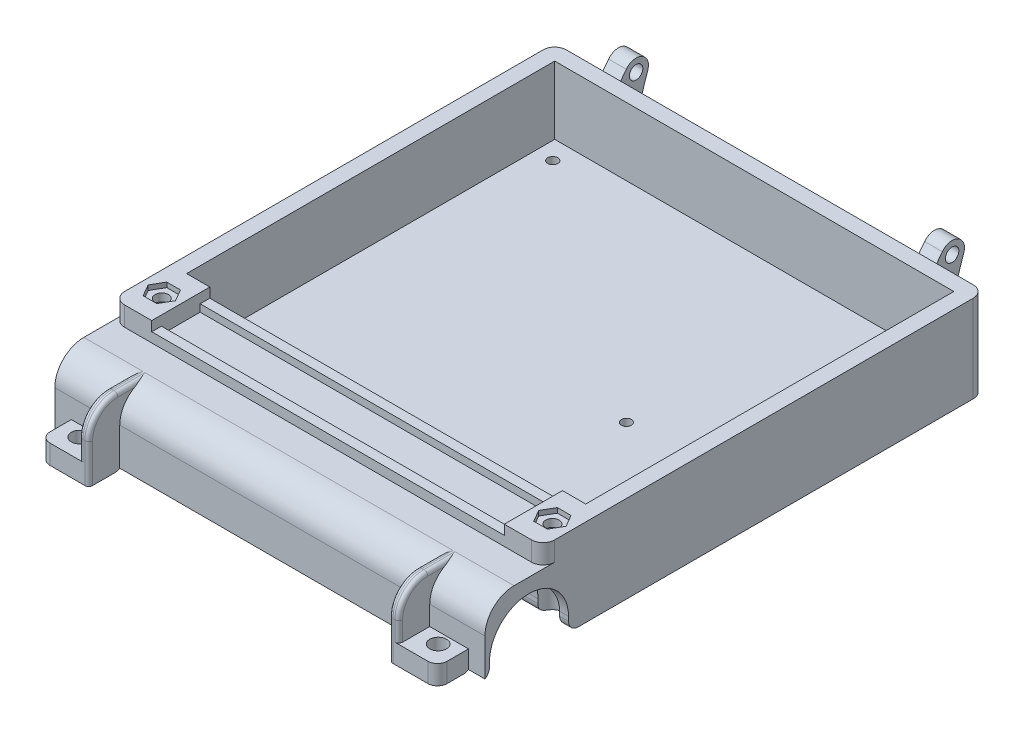
SolidWorks part; units mm, degrees
ref_plane "Front Plane" through (0, 0, 0) normal (0, 0, 1) x (1, 0, 0)
ref_plane "Top Plane" through (0, 0, 0) normal (0, 1, 0) x (1, 0, 0)
ref_plane "Right Plane" through (0, 0, 0) normal (1, 0, 0) x (0, 0, -1)
sketch "Sketch1" plane through (0, 0, 0) normal (0, 1, 0) x (1, 0, 0)
  line L1 (-65.405, -57.15) -> (65.405, -57.15) construction
  line L2 (-65.405, -57.15) -> (-65.405, 57.15) construction
  line L3 (-65.405, 57.15) -> (65.405, 57.15) construction
  line L4 (65.405, -57.15) -> (65.405, 57.15) construction
  line L5 (-65.405, -57.15) -> (65.405, 57.15) construction
  line L6 (-65.405, 57.15) -> (65.405, -57.15) construction
  line L7 (-70.485, 62.23) -> (70.485, 62.23)
  line L8 (-70.485, 62.23) -> (-70.485, -82.55)
  line L9 (-70.485, -82.55) -> (70.485, -82.55)
  line L10 (70.485, 62.23) -> (70.485, -82.55)
  circle A0 centre (61.595, 50.8) radius 1.65
  circle A1 centre (-59.69, 50.8) radius 1.65
  circle A2 centre (26.67, -11.43) radius 1.65
  point P0 (0, 0)
  dimension "D5" = 3.3
  dimension "D1" = 114.3
  dimension "D2" = 130.81
  dimension "D3" = 92.075
  dimension "D4" = 127
  dimension "D6" = 5.08
  dimension "D7" = 5.08
  dimension "D8" = 5.08
  dimension "D9" = 107.95
  dimension "D10" = 5.715
  dimension "D11" = 45.72
  dimension "D12" = 25.4
extrude "Boss-Extrude1" add sketch "Sketch1" along normal blind 6.35
sketch "Sketch2" plane through (0, 6.35, 0) normal (0, 1, 0) x (1, 0, 0)
  line L0 (70.485, -82.55) -> (70.485, 62.23) construction
  line L2 (-70.485, 62.23) -> (-70.485, -82.55) construction
  line L3 (70.485, 62.23) -> (-70.485, 62.23) construction
  line L4 (70.485, -82.55) -> (70.485, 62.23)
  line L5 (-70.485, -82.55) -> (70.485, -82.55)
  line L6 (-70.485, 62.23) -> (-70.485, -82.55)
  line L7 (70.485, 62.23) -> (-70.485, 62.23)
  line L8 (57.785, -79.375) -> (57.785, -66.675)
  line L9 (65.405, 57.15) -> (-65.405, 57.15)
  line L10 (-65.405, 57.15) -> (-65.405, -63.5)
  line L12 (-65.405, -63.5) -> (65.405, -63.5)
  line L13 (-57.785, -79.375) -> (57.785, -79.375)
  line L14 (57.785, -66.675) -> (-57.785, -66.675)
  line L15 (-57.785, -66.675) -> (-57.785, -79.375)
  line L16 (65.405, -63.5) -> (65.405, 57.15)
  dimension "D2" = 3.175
  dimension "D1" = 5.08
  dimension "D3" = 5.08
  dimension "D4" = 5.08
  dimension "D5" = 12.7
  dimension "D6" = 3.175
  dimension "D7" = 12.7
  dimension "D8" = 12.7
extrude "Boss-Extrude2" add sketch "Sketch2" along normal blind 22.225
sketch "Sketch3" plane through (0, 28.575, 0) normal (0, 1, 0) x (1, 0, 0)
  line L0 (-65.405, -63.5) -> (65.405, -63.5) construction
  line L1 (-57.785, -63.5) -> (57.785, -63.5)
  line L2 (-57.785, -63.5) -> (-57.785, -82.55)
  line L3 (-57.785, -82.55) -> (57.785, -82.55)
  line L4 (57.785, -63.5) -> (57.785, -82.55)
  line L5 (-70.485, -82.55) -> (70.485, -82.55) construction
  line L7 (57.785, -79.375) -> (57.785, -66.675) construction
  line L8 (-57.785, -66.675) -> (-57.785, -79.375) construction
extrude "Cut-Extrude1" cut sketch "Sketch3" against normal blind 3.175
sketch "Sketch4" plane through (0, 6.35, 0) normal (0, 1, 0) x (1, 0, 0)
  line L4 (-57.785, -66.675) -> (-57.785, -79.375)
  line L5 (-57.785, -79.375) -> (57.785, -79.375)
  line L6 (57.785, -79.375) -> (57.785, -66.675)
  line L7 (57.785, -66.675) -> (-57.785, -66.675)
  line L8 (-57.785, -66.675) -> (-57.785, -79.375)
  line L9 (-57.785, -79.375) -> (57.785, -79.375)
  line L10 (57.785, -79.375) -> (57.785, -66.675)
  line L11 (57.785, -66.675) -> (-57.785, -66.675)
  dimension "D1" = 0
extrude "Boss-Extrude3" add sketch "Sketch4" along normal offset from surface (16.6687 mm away) 2.3813 up to face at (0, 25.4, 65.0875)
ref_plane "Plane1" through (51.7855, 0, 0) normal (1, 0, 0) x (0, 0, -1)
sketch "Sketch5" plane through (51.7855, 0, 0) normal (1, 0, 0) x (0, 0, -1)
  line L0 (-82.55, 28.575) -> (62.23, 28.575) construction
  line L1 (69.3307, 32.075) -> (65.2893, 32.075) construction
  line L2 (65.2893, 32.075) -> (63.2685, 28.575) construction
  line L3 (63.2685, 28.575) -> (65.2893, 25.075) construction
  line L4 (65.2893, 25.075) -> (69.3307, 25.075) construction
  line L5 (69.3307, 25.075) -> (71.3515, 28.575) construction
  line L6 (71.3515, 28.575) -> (69.3307, 32.075) construction
  line L7 (62.23, 28.575) -> (62.23, 0) construction
  line L8 (62.23, 28.575) -> (64.0948, 31.0236)
  line L9 (62.23, 0) -> (62.23, 28.575)
  line L10 (62.23, 0) -> (71.1518, 27.3204)
  circle A0 centre (67.31, 28.575) radius 3.5 construction
  arc A1 (64.0948, 31.0236) -> (71.1518, 27.3204) centre (67.31, 28.575) cw
  circle A2 centre (67.31, 28.575) radius 2.2
  dimension "D3" = 4.4
  dimension "D1" = 5.08
  dimension "D2" = 7
extrude "Boss-Extrude4" add sketch "Sketch5" along normal mid plane 5.8
mirror "Mirror1" about plane through (0, 0, 0) normal (1, 0, 0) of "Boss-Extrude4"
sketch "Sketch6" plane through (0, 0, 82.55) normal (0, 0, 1) x (1, 0, 0)
  line L0 (70.485, 28.575) -> (70.485, 0) construction
  line L1 (-70.485, 0) -> (70.485, 0)
  line L2 (-70.485, 0) -> (-70.485, 22.225)
  line L3 (-70.485, 22.225) -> (70.485, 22.225)
  line L4 (70.485, 0) -> (70.485, 22.225)
  dimension "D1" = 22.225
extrude "Boss-Extrude5" add sketch "Sketch6" along normal blind 19.05
sketch "Sketch7" plane through (0, 0, 0) normal (0, -1, 0) x (1, 0, 0)
  line L0 (0, 0) -> (0, 146.1519) construction
  line L1 (-70.485, 101.6) -> (70.485, 101.6) construction
  line L2 (52.3875, 101.6) -> (65.0875, 101.6)
  line L3 (52.3875, 101.6) -> (52.3875, 111.76)
  line L4 (52.3875, 111.76) -> (65.0875, 111.76)
  line L5 (65.0875, 101.6) -> (65.0875, 111.76)
  line L6 (52.3875, 105.2) -> (58.7375, 105.2) construction
  line L7 (58.7375, 105.2) -> (65.0875, 105.2) construction
  line L8 (-58.7375, 105.2) -> (-65.0875, 105.2) construction
  line L9 (-52.3875, 105.2) -> (-58.7375, 105.2) construction
  line L10 (-65.0875, 101.6) -> (-65.0875, 111.76)
  line L11 (-52.3875, 111.76) -> (-65.0875, 111.76)
  line L12 (-52.3875, 101.6) -> (-52.3875, 111.76)
  line L13 (-52.3875, 101.6) -> (-65.0875, 101.6)
  circle A0 centre (58.7375, 105.2) radius 2.75
  circle A1 centre (-58.7375, 105.2) radius 2.75
  dimension "D1" = 5.5
  dimension "D4" = 3.6
  dimension "D2" = 117.475
  dimension "D3" = 12.7
  dimension "D5" = 10.16
extrude "Boss-Extrude6" add sketch "Sketch7" against normal blind 6.35
sketch "Sketch8" plane through (70.485, 0, 0) normal (1, 0, 0) x (0, 0, -1)
  line L0 (-101.6, 0) -> (-111.76, 0) construction
  line L1 (-100.12, 4.572) -> (-100.12, 0)
  line L2 (-101.6, 0) -> (62.23, 0) construction
  line L3 (-100.12, 0) -> (-74.212, 0)
  line L4 (-74.212, 0) -> (-74.212, 4.572)
  line L5 (-107.95, 0) -> (-102.45, 0) construction
  line L6 (-107.95, 0) -> (-102.45, 0) construction
  line L7 (-105.2, 0) -> (-105.2, 50000) construction
  arc A0 (-74.212, 4.572) -> (-100.12, 4.572) centre (-87.166, 4.572) ccw
  point P2 (-87.166, 17.526)
  point P20 (-105.2, 0)
  dimension "D1" = 25.908
  dimension "D2" = 17.526
  dimension "D3" = 18.034
extrude "Cut-Extrude2" cut sketch "Sketch8" against normal through all
sketch "Sketch9" plane through (0, 28.575, 0) normal (0, 1, 0) x (1, 0, 0)
  line L0 (0, -101.6) -> (0, 49898.4) construction
  line L1 (70.485, -101.6) -> (-70.485, -101.6) construction
  line L2 (57.785, -82.55) -> (70.485, -82.55) construction
  circle A0 centre (64.008, -73.025) radius 2.2
  circle A1 centre (-64.008, -73.025) radius 2.2
  point P4 (0, -101.6)
  dimension "D1" = 64.008
  dimension "D3" = 4.4
  dimension "D2" = 9.525
extrude "Cut-Extrude3" cut sketch "Sketch9" against normal through all
sketch "Sketch10" plane through (0, 0, 0) normal (0, -1, 0) x (1, 0, 0)
  line L1 (29.801, 13.2377) -> (26.67, 15.0454)
  line L2 (26.67, 15.0454) -> (23.539, 13.2377)
  line L3 (23.539, 13.2377) -> (23.539, 9.6223)
  line L4 (23.539, 9.6223) -> (26.67, 7.8146)
  line L5 (26.67, 7.8146) -> (29.801, 9.6223)
  line L6 (29.801, 9.6223) -> (29.801, 13.2377)
  line L7 (61.595, -47.1846) -> (58.464, -48.9923)
  line L8 (58.464, -48.9923) -> (58.464, -52.6077)
  line L9 (58.464, -52.6077) -> (61.595, -54.4154)
  line L10 (61.595, -54.4154) -> (64.726, -52.6077)
  line L11 (64.726, -52.6077) -> (64.726, -48.9923)
  line L12 (64.726, -48.9923) -> (61.595, -47.1846)
  line L13 (-56.559, -48.9923) -> (-59.69, -47.1846)
  line L14 (-59.69, -47.1846) -> (-62.821, -48.9923)
  line L15 (-62.821, -48.9923) -> (-62.821, -52.6077)
  line L16 (-62.821, -52.6077) -> (-59.69, -54.4154)
  line L17 (-59.69, -54.4154) -> (-56.559, -52.6077)
  line L18 (-56.559, -52.6077) -> (-56.559, -48.9923)
  circle A0 centre (26.67, 11.43) radius 3.131 construction
  circle A1 centre (61.595, -50.8) radius 3.131 construction
  circle A2 centre (-59.69, -50.8) radius 3.131 construction
  dimension "D1" = 6.262
extrude "Cut-Extrude4" cut sketch "Sketch10" against normal blind 3.175
sketch "Sketch11" plane through (0, 28.575, 0) normal (0, 1, 0) x (1, 0, 0)
  line L1 (66.2487, -69.144) -> (61.7673, -69.144)
  line L2 (61.7673, -69.144) -> (59.5266, -73.025)
  line L3 (59.5266, -73.025) -> (61.7673, -76.906)
  line L4 (61.7673, -76.906) -> (66.2487, -76.906)
  line L5 (66.2487, -76.906) -> (68.4894, -73.025)
  line L6 (68.4894, -73.025) -> (66.2487, -69.144)
  line L7 (-61.7673, -69.144) -> (-66.2487, -69.144)
  line L8 (-66.2487, -69.144) -> (-68.4894, -73.025)
  line L9 (-68.4894, -73.025) -> (-66.2487, -76.906)
  line L10 (-66.2487, -76.906) -> (-61.7673, -76.906)
  line L11 (-61.7673, -76.906) -> (-59.5266, -73.025)
  line L12 (-59.5266, -73.025) -> (-61.7673, -69.144)
  circle A0 centre (64.008, -73.025) radius 3.881 construction
  circle A1 centre (-64.008, -73.025) radius 3.881 construction
  dimension "D1" = 7.762
extrude "Cut-Extrude5" cut sketch "Sketch11" against normal blind 1.5875
sketch "Sketch12" plane through (0, 0, 0) normal (0, -1, 0) x (1, 0, 0)
  circle A0 centre (-64.008, 73.025) radius 3.75
  circle A1 centre (64.008, 73.025) radius 3.75
  dimension "D1" = 7.5
extrude "Cut-Extrude6" cut sketch "Sketch12" against normal offset from surface (24.4475 mm away) 2.54 up to face at (-64.008, 26.9875, 73.025)
sketch "Sketch13" plane through (0, 0, 0) normal (0, -1, 0) x (1, 0, 0)
  line L0 (-52.3875, 111.76) -> (-65.0875, 111.76) construction
  line L1 (52.3875, 101.6) -> (49.2125, 101.6)
  line L2 (52.3875, 101.6) -> (52.3875, 111.76)
  line L3 (52.3875, 111.76) -> (49.2125, 111.76)
  line L4 (49.2125, 101.6) -> (49.2125, 111.76)
  line L5 (-52.3875, 101.6) -> (-49.2125, 101.6)
  line L6 (-52.3875, 101.6) -> (-52.3875, 111.76)
  line L7 (-52.3875, 111.76) -> (-49.2125, 111.76)
  line L8 (-49.2125, 101.6) -> (-49.2125, 111.76)
  dimension "D1" = 3.175
extrude "Boss-Extrude7" add sketch "Sketch13" against normal up to surface (22.225 mm away) up to face at (0, 22.225, 92.075)
fillet "Fillet1" radius 3.175 6 edges at (-65.0875, 3.175, 111.76) (65.0875, 3.175, 111.76) (-69.0251, 0, 74.212) (69.0251, 0, 74.212) (0, 0, 74.212) (0, 0, 100.12)
fillet "Fillet2" radius 9.525 5 edges at (50.8, 22.225, 111.76) (-50.8, 22.225, 111.76) (61.4363, 22.225, 101.6) (-61.4362, 22.225, 101.6) (0, 22.225, 101.6)
fillet "Fillet3" radius 1.27 12 edges at (49.2125, 6.35, 111.76) (49.2125, 22.225, 97.155) (52.3875, 22.225, 97.155) (52.3875, 9.525, 111.76) (-52.3875, 9.525, 111.76) (-52.3875, 22.225, 97.155) (-49.2125, 22.225, 97.155) (-49.2125, 6.35, 111.76) (49.2125, 19.4352, 108.9702) (52.3875, 19.4352, 108.9702) (-52.3875, 19.4352, 108.9702) (-49.2125, 19.4352, 108.9702)
fillet "Fillet4" radius 3.81 4 edges at (-70.485, 14.2875, -62.23) (70.485, 14.2875, -62.23) (-70.485, 25.4, 82.55) (70.485, 25.4, 82.55)
